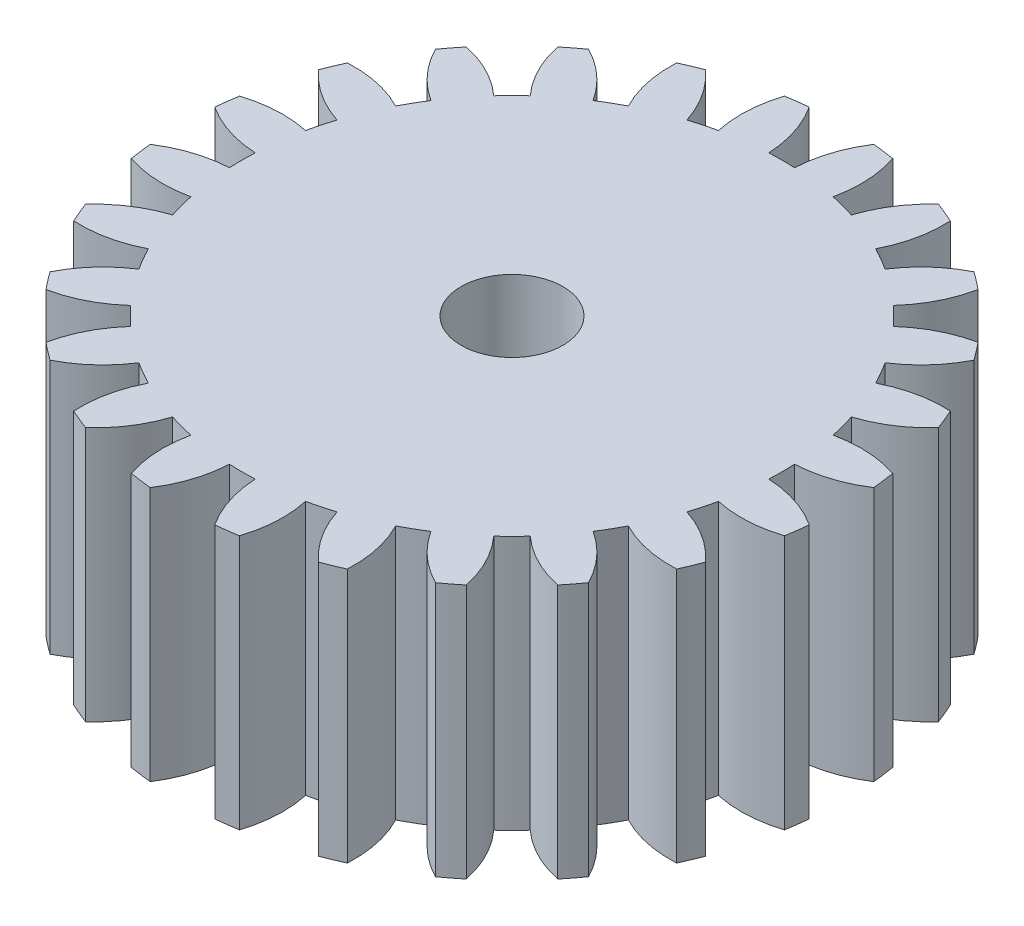
SolidWorks part; units mm, degrees
ref_plane "Front Plane" through (0, 0, 0) normal (0, 0, 1) x (1, 0, 0)
ref_plane "Top Plane" through (0, 0, 0) normal (0, 1, 0) x (1, 0, 0)
ref_plane "Right Plane" through (0, 0, 0) normal (1, 0, 0) x (0, 0, -1)
sketch "Sketch1" plane through (0, 0, 0) normal (0, 1, 0) x (1, 0, 0)
  circle A0 centre (0, 0) radius 6
  circle A1 centre (0, 0) radius 6.5
  circle A2 centre (0, 0) radius 5.3
  dimension "D1" = 12
  dimension "D2" = 13
  dimension "D3" = 1.2
extrude "Boss-Extrude1" add sketch "Sketch1" along normal mid plane 5 contours A1 A0 | A0 A2 | A2 region at (-5.8303, 0, 0) region at (-6.3162, 0, 0) region at (0, 0, 0)
sketch "Sketch3" plane through (0, 0, 0) normal (0, 1, 0) x (1, 0, 0)
  line L0 (0, 0) -> (0, 6.5) construction
  line L1 (-0.3924, 5.9872) -> (0.3924, 5.9872) construction
  line L2 (-0.253, 5.294) -> (0, 0) construction
  line L3 (0, 4.909) -> (-1.017, 7.7032) construction
  line L4 (0, 0) -> (0.8484, 6.4444) construction
  line L5 (0.3924, 5.9872) -> (1.1705, 5.8847) construction
  circle A0 centre (0, 0) radius 6.5 construction
  arc A1 (-2.0974, 7.4816) -> (-0.253, 5.294) centre (-2.606, 5.1815) cw
  arc A2 (2.0974, 7.4816) -> (0.253, 5.294) centre (2.606, 5.1815) ccw
  circle A3 centre (0, 0) radius 5.3 construction
  arc A4 (0.253, 5.294) -> (-0.253, 5.294) centre (0, 0) ccw
  circle A5 centre (0, 0) radius 6 construction
  circle A6 centre (0, 0) radius 6.5 construction
  circle A7 centre (0, 0) radius 7.77
  arc A8 (2.0974, 7.4816) -> (-2.0974, 7.4816) centre (0, 0) ccw
  dimension "D2" = 20
  dimension "D3" = 7.5
  dimension "D1" = 1.27
extrude "Cut-Extrude1" cut sketch "Sketch3" against normal through all both and the other way through all
fillet "Fillet2" [suppressed] radius 0.15
pattern_circular "CirPattern1" count 24 over 360 about axis through (0, 2.5, 0) along (0, 1, 0) of "Cut-Extrude1", "Fillet2"
sketch "Sketch4" plane through (0, 0, 0) normal (0, 1, 0) x (1, 0, 0)
  circle A0 centre (0, 0) radius 1
  dimension "D1" = 2
extrude "Cut-Extrude2" cut sketch "Sketch4" along normal through all both and the other way through all
equation "\"Module\"= .5"
equation "\"Number of Teeth\"= 24"
equation "\"D1@Sketch1\"=\"Module\"* \"Number of Teeth\""
equation "\"D2@Sketch1\"=(\"Number of Teeth\" + 2) * \"Module\""
equation "\"D3@Sketch1\"=\"Module\" * if( \"Module\" => 1.25, 2.25, 2.4)"
equation "\"D3@Sketch3\"=180 / \"Number of Teeth\""
equation "\"D1@Fillet2\"=.3 * \"Module\""
equation "\"D1@CirPattern1\"=\"Number of Teeth\""
